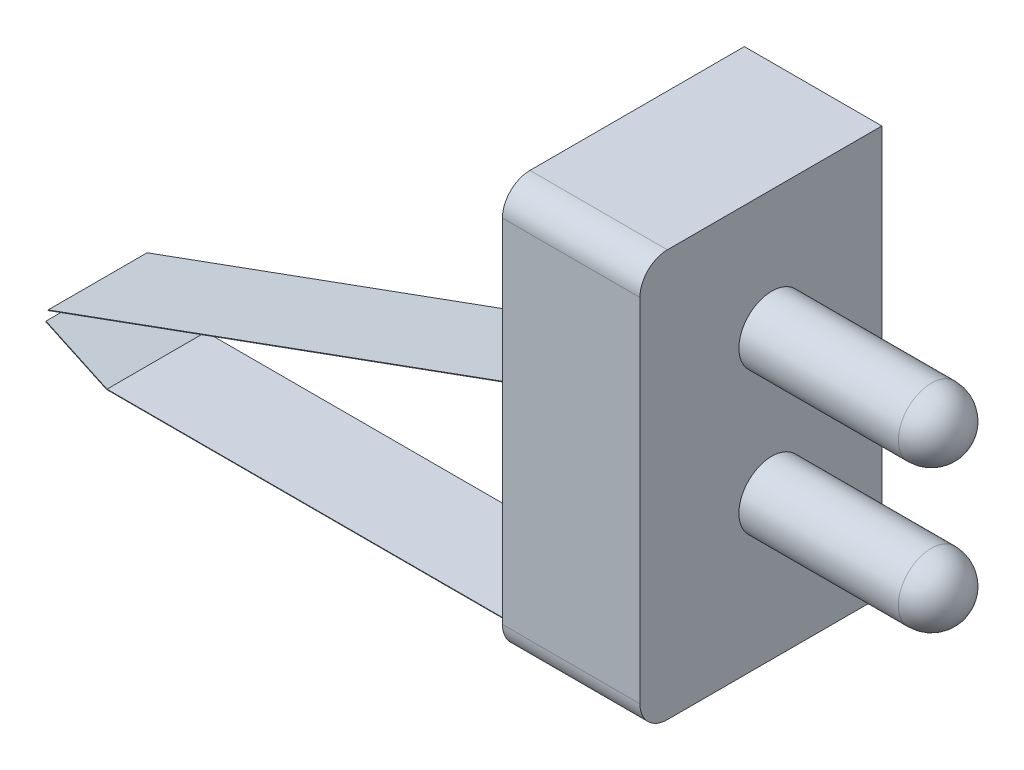
SolidWorks part; units mm, degrees
material "Nickel"
ref_plane "Front Plane" through (0, 0, 0) normal (0, 0, 1) x (1, 0, 0)
ref_plane "Top Plane" through (0, 0, 0) normal (0, 1, 0) x (1, 0, 0)
ref_plane "Right Plane" through (0, 0, 0) normal (1, 0, 0) x (0, 0, -1)
sketch "Sketch1" plane through (0, 0, 0) normal (1, 0, 0) x (0, 0, -1)
  line L1 (-4.318, -9.398) -> (5.588, -9.398)
  line L2 (-5.588, -8.128) -> (-5.588, 8.128)
  line L3 (-4.318, 9.398) -> (5.588, 9.398)
  line L4 (5.588, -9.398) -> (5.588, 9.398)
  line L5 (-5.588, -9.398) -> (5.588, 9.398) construction
  line L6 (-5.588, 9.398) -> (5.588, -9.398) construction
  arc A0 (-4.318, -9.398) -> (-5.588, -8.128) centre (-4.318, -8.128) cw
  arc A1 (-4.318, 9.398) -> (-5.588, 8.128) centre (-4.318, 8.128) ccw
  point P0 (0, 0)
  dimension "D3" = 1.27
  dimension "D1" = 18.796
  dimension "D2" = 11.176
extrude "Boss-Extrude1" add sketch "Sketch1" against normal blind 6.35
sketch "Sketch2" plane through (0, 0, 0) normal (1, 0, 0) x (0, 0, -1)
  line L0 (5.588, -9.398) -> (5.588, 9.398) construction
  line L1 (-4.318, -9.398) -> (5.588, -9.398) construction
  circle A0 centre (0.508, -2.794) radius 1.524
  circle A1 centre (0.508, 3.81) radius 1.524
  point P4 (0, 0)
  dimension "D1" = 3.048
  dimension "D4" = 3.556
  dimension "D2" = 6.604
  dimension "D3" = 8.128
extrude "Boss-Extrude2" add sketch "Sketch2" along normal blind 7.366
dome "Dome1" faces to dome 1 distance 1.524 reverse direction no elliptical dome no face at (7.366, 3.81, -2.032) parameters "D1"=1.524
dome "Dome2" faces to dome 1 distance 1.524 reverse direction no elliptical dome no face at (7.366, -2.794, -2.032) parameters "D1"=1.524
ref_plane "Plane1" through (0, 0, 1.778) normal (0, 0, 1) x (1, 0, 0)
sketch "Sketch6" plane through (0, 0, 1.778) normal (0, 0, 1) x (1, 0, 0)
  line L0 (-6.35, -3.3915) -> (-6.35, -9.684)
  line L1 (-6.35, 8.128) -> (-6.35, -8.128) construction
  line L2 (-6.35, -9.398) -> (0, -9.398) construction
  line L3 (-8.35, -11.684) -> (-28.448, -11.684)
  line L4 (-28.448, -11.684) -> (-31.242, -10.3811)
  line L5 (-6.35, -3.3915) -> (-6.3754, -3.3915)
  line L6 (-6.3754, -3.3915) -> (-6.3754, -9.684)
  line L7 (-8.35, -11.6586) -> (-28.4248, -11.6586)
  line L8 (-28.4248, -11.6586) -> (-31.242, -10.3443)
  line L9 (-31.242, -10.3443) -> (-31.242, -10.3811)
  arc A0 (-6.35, -9.684) -> (-8.35, -11.684) centre (-8.35, -9.684) cw
  arc A1 (-6.3754, -9.684) -> (-8.35, -11.6586) centre (-8.35, -9.684) cw
  point P10 (-6.35, -11.684)
  point P15 (-6.604, -9.684)
  point P18 (-8.35, -11.43)
  point P19 (-8.35, -11.6586)
  dimension "D2" = 2
  dimension "D1" = 2.286
  dimension "D3" = 24.892
  dimension "D4" = 22.098
  dimension "D5" = 0.01
  dimension "D6" = 0.0254
  dimension "D7" = 0.0254
  dimension "D8" = 155
extrude "Boss-Extrude3" add sketch "Sketch6" against normal blind 4.572
sketch "Sketch7" plane through (0, 0, 1.778) normal (0, 0, 1) x (1, 0, 0)
  line L0 (-6.35, 5.1713) -> (-6.35, -0.8515)
  line L1 (-6.35, 8.128) -> (-6.35, -8.128) construction
  line L2 (-6.35, -0.8515) -> (-31.1442, -9.8758)
  line L3 (-6.3754, 5.1713) -> (-6.3754, -0.8337)
  line L4 (-6.3754, -0.8337) -> (-31.1442, -9.8488)
  line L5 (-31.1442, -9.8488) -> (-31.1442, -9.8758)
  arc A0 (-6.35, 5.1713) -> (-6.3754, 5.1713) centre (-6.3627, 5.1713) ccw
  dimension "D1" = 2.54
  dimension "D2" = 110
  dimension "D3" = 0.0254
  dimension "D4" = 0.0254
extrude "Boss-Extrude4" add sketch "Sketch7" against normal blind 4.572
